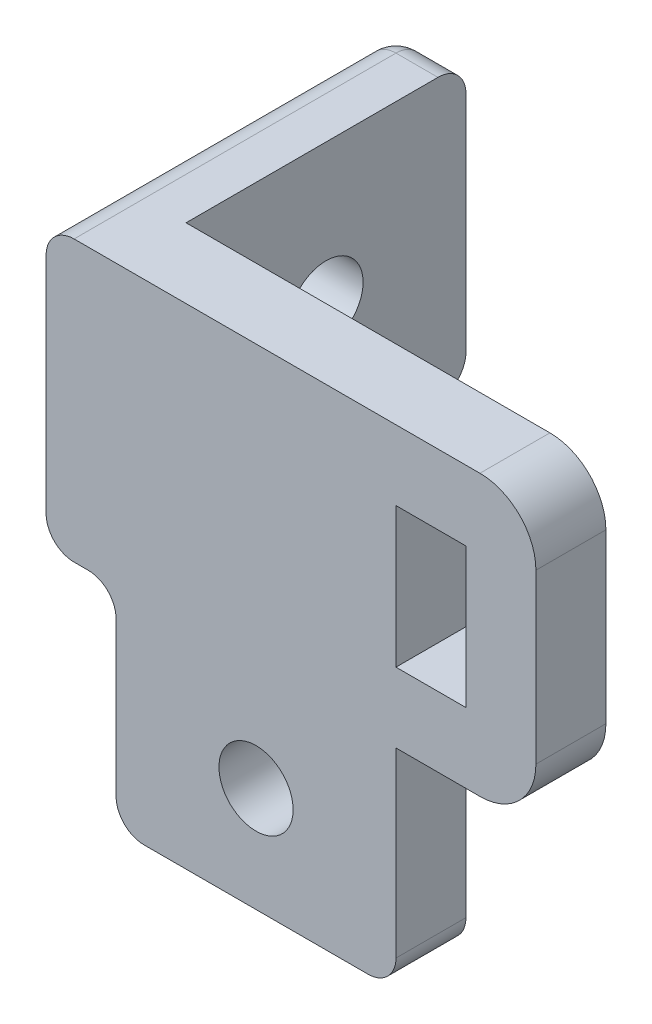
SolidWorks part; units mm, degrees
material "ABS"
ref_plane "Alzado" through (0, 0, 0) normal (0, 0, 1) x (1, 0, 0)
ref_plane "Planta" through (0, 0, 0) normal (0, 1, 0) x (1, 0, 0)
ref_plane "Vista lateral" through (0, 0, 0) normal (1, 0, 0) x (0, 0, -1)
sketch "Croquis1" plane through (0, 0, 0) normal (0, 0, 1) x (1, 0, 0)
  line L1 (-15, -10) -> (11, -10)
  line L2 (-15, -10) -> (-15, 10)
  line L3 (-15, 10) -> (11, 10)
  line L4 (15, -6) -> (15, 6)
  line L5 (-15, -10) -> (15, 10) construction
  line L6 (-15, 10) -> (15, -10) construction
  line L7 (5, 5) -> (10, 5)
  line L8 (5, 5) -> (5, -5)
  line L9 (5, -5) -> (10, -5)
  line L10 (10, 5) -> (10, -5)
  arc A1 (15, -6) -> (11, -10) centre (11, -6) cw
  arc A2 (15, 6) -> (11, 10) centre (11, 6) ccw
  point P0 (0, 0)
  dimension "D10" = 4
  dimension "D1" = 30
  dimension "D2" = 20
  dimension "D5" = 10
  dimension "D6" = 5
  dimension "D8" = 5
extrude "Saliente-Extruir1" add sketch "Croquis1" along normal blind 5 contours L10 L7 L8 L9 | L3 A2 L4 A1 L1 L2 region at (7.5, 0, 0)
sketch "Croquis2" plane through (0, 0, 5) normal (0, 0, 1) x (1, 0, 0)
  line L0 (-15, -10) -> (-15, 10) construction
  line L1 (-15, 10) -> (-20, 10)
  line L2 (-15, 10) -> (-15, -10)
  line L3 (-15, -10) -> (-20, -10)
  line L4 (-20, 10) -> (-20, -10)
  dimension "D1" = 5
extrude "Saliente-Extruir3" add sketch "Croquis2" against normal blind 25
sketch "Croquis3" plane through (-20, 0, 0) normal (-1, 0, 0) x (0, 0, 1)
  line L0 (-20, 10) -> (-20, -10) construction
  circle A0 centre (-10, 0) radius 2.65
  dimension "D1" = 5.3
  dimension "D2" = 10
extrude "Cortar-Extruir1" cut sketch "Croquis3" against normal through all
sketch "Croquis4" plane through (0, 0, 5) normal (0, 0, 1) x (1, 0, 0)
  line L0 (-15, -10) -> (-15, -25)
  line L1 (-15, -10) -> (5, -10)
  line L3 (-15, -25) -> (5, -25)
  line L4 (5, -10) -> (5, -25)
  line L5 (-20, 10) -> (-20, -10) construction
  circle A0 centre (-5, -17.5) radius 2.65
  dimension "D3" = 5.3
  dimension "D4" = 10
  dimension "D5" = 7.5
  dimension "D6" = 5
extrude "Saliente-Extruir4" add sketch "Croquis4" against normal blind 5
fillet "Redondeo1" radius 2 1 edges at (-15, -10, 2.5)
fillet "Redondeo2" radius 2 2 edges at (5, -25, 2.5) (-15, -25, 2.5)
fillet "Redondeo3" radius 2 2 edges at (-17.5, 10, -20) (-17.5, -10, -20)
fillet "Redondeo4" radius 2 5 edges at (-20, -10, -6.5) (-20, -9.4142, -19.4142) (-20, 0, -20) (-20, 9.4142, -19.4142) (-20, 10, -6.5)
